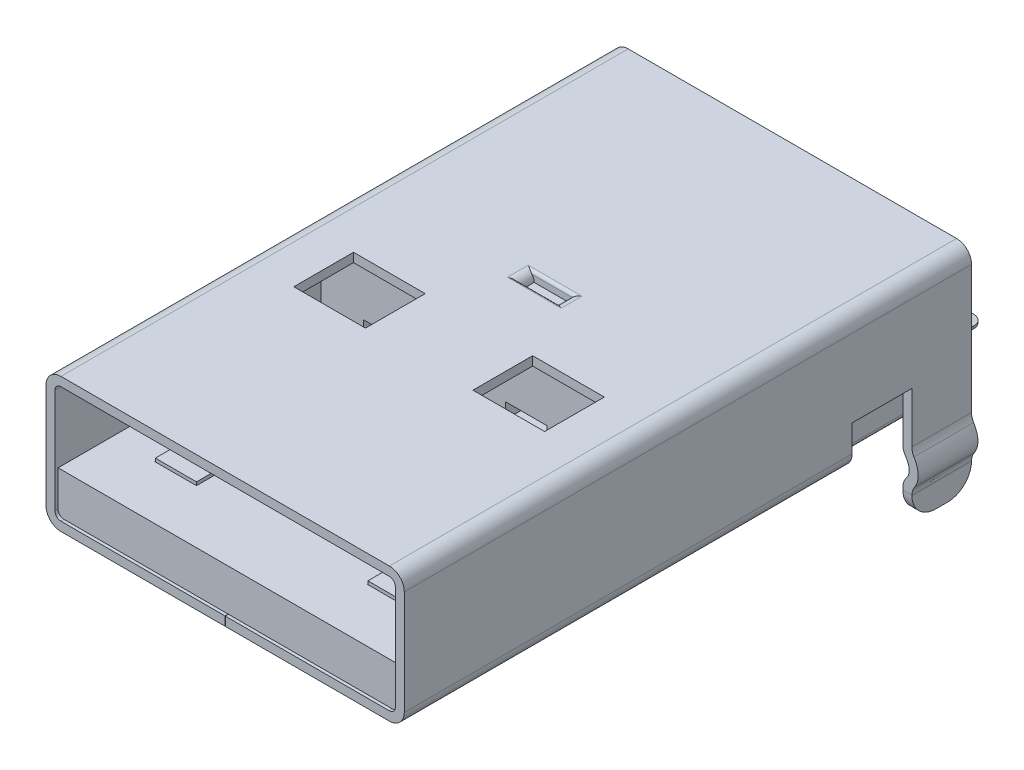
SolidWorks part; units mm, degrees
ref_plane "Front Plane" through (0, 0, 0) normal (0, 0, 1) x (1, 0, 0)
ref_plane "Top Plane" through (0, 0, 0) normal (0, 1, 0) x (1, 0, 0)
ref_plane "Right Plane" through (0, 0, 0) normal (1, 0, 0) x (0, 0, -1)
sketch "Sketch1" plane through (0, 0, 0) normal (0, 0, 1) x (1, 0, 0)
  line L4 (6, -1.75) -> (6, 1.75)
  line L5 (5.5, 2.25) -> (-5.5, 2.25)
  line L6 (-6, 1.75) -> (-6, -1.75)
  line L15 (-5.5, -2.25) -> (5.5, -2.25)
  line L16 (-5.5, -1.95) -> (5.5, -1.95)
  line L17 (5.7, -1.75) -> (5.7, 1.75)
  line L18 (5.5, 1.95) -> (-5.5, 1.95)
  line L19 (-5.7, 1.75) -> (-5.7, -1.75)
  arc A0 (5.5, -2.25) -> (6, -1.75) centre (5.5, -1.75) ccw
  arc A1 (6, 1.75) -> (5.5, 2.25) centre (5.5, 1.75) ccw
  arc A2 (-5.5, 2.25) -> (-6, 1.75) centre (-5.5, 1.75) ccw
  arc A3 (-6, -1.75) -> (-5.5, -2.25) centre (-5.5, -1.75) ccw
  arc A7 (5.5, -1.95) -> (5.7, -1.75) centre (5.5, -1.75) ccw
  arc A8 (5.7, 1.75) -> (5.5, 1.95) centre (5.5, 1.75) ccw
  arc A9 (-5.5, 1.95) -> (-5.7, 1.75) centre (-5.5, 1.75) ccw
  arc A10 (-5.7, -1.75) -> (-5.5, -1.95) centre (-5.5, -1.75) ccw
extrude "Boss-Extrude1" add sketch "Sketch1" against normal blind 19
sketch "Sketch2" plane through (6, 0, 0) normal (1, 0, 0) x (0, 0, -1)
  line L0 (17, -1.25) -> (17, -0.85)
  line L1 (17, -0.85) -> (15, -0.85)
  line L2 (15, -2.25) -> (15, -1.75)
  line L3 (15, -0.85) -> (15, -1.75)
  line L4 (17, -1.25) -> (17, -1.75)
  line L5 (19, -2.25) -> (0, -2.25) construction
  line L6 (17, -2.25) -> (15, -2.25)
  line L7 (17, -1.75) -> (19, -1.75)
  line L8 (19, -1.75) -> (19, -2.25)
  line L9 (19, -2.25) -> (17, -2.25)
extrude "Cut-Extrude1" cut sketch "Sketch2" against normal through all
sketch "Sketch3" plane through (0, 0, -17) normal (0, 0, 1) x (1, 0, 0)
  line L0 (5.7, -3.9471) -> (5.7, -4.7471)
  line L1 (5.7, -4.7471) -> (6, -4.7471)
  line L2 (6, -4.7471) -> (6, -3.9598)
  line L3 (-6, -3.9598) -> (-6, -4.7471)
  line L4 (-6, -4.7471) -> (-5.7, -4.7471)
  line L5 (-5.7, -4.7471) -> (-5.7, -3.9471)
  line L6 (6, -2.5479) -> (6, -1.75)
  line L7 (5.7, -1.75) -> (5.7, -2.6346)
  line L8 (5.7, -3.8595) -> (5.7, -3.9471)
  line L9 (-6, -1.75) -> (-6, -2.5479)
  line L10 (-5.7, -3.9471) -> (-5.7, -3.8595)
  line L11 (-5.7, -2.6346) -> (-5.7, -1.75)
  line L12 (6, -1.75) -> (5.7, -1.75)
  line L13 (-6, -1.75) -> (-5.7, -1.75)
  spline S0 degree 3 poles (6, -3.9598) (6, -3.9556) (6.0001, -3.9513) (6.0002, -3.9471) knots 0 0 0 0 0.000013 0.000013 0.000013 0.000013 weights 1 1 1 1
  spline S1 degree 3 poles (-6.0002, -3.9471) (-6.0001, -3.9513) (-6, -3.9556) (-6, -3.9598) knots 0 0 0 0 0.000013 0.000013 0.000013 0.000013 weights 1 1 1 1
  spline S2 degree 3 poles (6.0707, -2.8043) (6.0247, -2.7272) (6, -2.6376) (6, -2.5479) knots 0 0 0 0 0.000269 0.000269 0.000269 0.000269 weights 1 1 1 1
  spline S3 degree 3 poles (5.7, -2.6346) (5.7, -2.7328) (5.7297, -2.8307) (5.7842, -2.9124) knots 0 0 0 0 0.000295 0.000295 0.000295 0.000295 weights 1 1 1 1
  spline S4 degree 3 poles (5.7842, -2.9124) (5.8959, -3.0796) (5.9405, -3.3024) (5.8728, -3.4711) (5.8159, -3.5394) knots 0 0 0 0 0.000386 0.000676 0.000676 0.000676 0.000676 weights 1 1 1 1 1
  spline S5 degree 3 poles (5.8159, -3.5394) (5.7418, -3.6283) (5.7, -3.7437) (5.7, -3.8595) knots 0 0 0 0 0.000348 0.000348 0.000348 0.000348 weights 1 1 1 1
  spline S6 degree 3 poles (6.0002, -3.9471) (6.0027, -3.851) (6.0335, -3.7558) (6.0879, -3.6766) knots 0 0 0 0 0.000288 0.000288 0.000288 0.000288 weights 1 1 1 1
  spline S7 degree 3 poles (6.0879, -3.6766) (6.255, -3.4335) (6.2625, -3.1253) (6.0707, -2.8043) knots 0 0 0 0 0.000918 0.000918 0.000918 0.000918 weights 1 1 1 1
  spline S8 degree 3 poles (-6, -2.5479) (-6, -2.6376) (-6.0247, -2.7272) (-6.0707, -2.8043) knots 0 0 0 0 0.000269 0.000269 0.000269 0.000269 weights 1 1 1 1
  spline S9 degree 3 poles (-6.0707, -2.8043) (-6.2625, -3.1253) (-6.255, -3.4335) (-6.0879, -3.6766) knots 0 0 0 0 0.00092 0.00092 0.00092 0.00092 weights 1 1 1 1
  spline S10 degree 3 poles (-6.0879, -3.6766) (-6.0335, -3.7558) (-6.0027, -3.851) (-6.0002, -3.9471) knots 0 0 0 0 0.000289 0.000289 0.000289 0.000289 weights 1 1 1 1
  spline S11 degree 3 poles (-5.7, -3.8595) (-5.7, -3.7437) (-5.7418, -3.6283) (-5.8159, -3.5394) knots 0 0 0 0 0.000348 0.000348 0.000348 0.000348 weights 1 1 1 1
  spline S12 degree 3 poles (-5.8159, -3.5394) (-5.8538, -3.4938) (-5.904, -3.3995) (-5.9248, -3.2089) (-5.868, -3.0378) (-5.7842, -2.9124) knots 0 0 0 0 0.000194 0.000388 0.000679 0.000679 0.000679 0.000679 weights 1 1 1 1 1 1
  spline S13 degree 3 poles (-5.7842, -2.9124) (-5.7297, -2.8307) (-5.7, -2.7328) (-5.7, -2.6346) knots 0 0 0 0 0.000295 0.000295 0.000295 0.000295 weights 1 1 1 1
  point P28 (6, -1.75)
extrude "Boss-Extrude2" add sketch "Sketch3" against normal up to surface (2 mm away) up to face at (0, 0.7242, -19)
fillet "Fillet1" radius 0.8 4 edges at (-5.85, -4.7471, -17) (-5.85, -4.7471, -19) (5.85, -4.7471, -17) (5.85, -4.7471, -19)
sketch "Sketch4" plane through (0, 2.25, 0) normal (0, 1, 0) x (1, 0, 0)
  line L0 (-1.8, 6.5) -> (-4.2, 6.5)
  line L1 (-4.2, 6.5) -> (-4.2, 8.5)
  line L2 (-4.2, 8.5) -> (-1.8, 8.5)
  line L3 (1.8, 6.5) -> (1.8, 8.5)
  line L4 (4.2, 6.5) -> (1.8, 6.5)
  line L5 (4.2, 8.5) -> (4.2, 6.5)
  line L6 (1.8, 8.5) -> (4.2, 8.5)
  line L7 (-1.8, 8.5) -> (-1.8, 6.5)
extrude "Cut-Extrude2" cut sketch "Sketch4" against normal through all
sketch "Sketch5" plane through (0, -2.25, 0) normal (0, -1, 0) x (1, 0, 0)
  line L1 (0.1311, -3.1511) -> (0.6409, -2.9635)
  line L2 (0.91, -3.1511) -> (0.91, -4.3489)
  line L3 (0.6409, -4.5365) -> (0.1311, -4.3489)
  line L5 (0.1311, -10.6511) -> (0.6409, -10.4635)
  line L6 (0.91, -10.6511) -> (0.91, -11.8489)
  line L7 (0.6409, -12.0365) -> (0.1311, -11.8489)
  line L10 (0.1345, -3.1605) -> (0.6444, -2.9728)
  line L11 (0.9, -3.1511) -> (0.9, -4.3489)
  line L12 (0.6444, -4.5272) -> (0.1345, -4.3395)
  line L14 (0.1345, -10.6605) -> (0.6444, -10.4728)
  line L15 (0.9, -10.6511) -> (0.9, -11.8489)
  line L16 (0.6444, -12.0272) -> (0.1345, -11.8395)
  line L19 (0.005, 0) -> (-0.005, 0)
  line L20 (0, -3.0666) -> (-0.005, 0)
  line L21 (0.01, -11.9334) -> (0.01, -15)
  line L22 (-5.5, -15) -> (5.5, -15) construction
  line L23 (0, -11.9334) -> (0, -15)
  line L24 (0.01, -3.0666) -> (0.005, 0)
  line L25 (0.01, -4.4334) -> (0.01, -10.5666)
  line L26 (0, -15) -> (0.01, -15)
  line L27 (0, -10.5666) -> (0, -4.4334)
  arc A0 (0.01, -3.0666) -> (0.1311, -3.1511) centre (0.1, -3.0666) ccw
  arc A1 (0.91, -3.1511) -> (0.6409, -2.9635) centre (0.71, -3.1511) ccw
  arc A2 (0.6409, -4.5365) -> (0.91, -4.3489) centre (0.71, -4.3489) ccw
  arc A3 (0.1311, -4.3489) -> (0.01, -4.4334) centre (0.1, -4.4334) ccw
  arc A4 (0.01, -10.5666) -> (0.1311, -10.6511) centre (0.1, -10.5666) ccw
  arc A5 (0.91, -10.6511) -> (0.6409, -10.4635) centre (0.71, -10.6511) ccw
  arc A6 (0.6409, -12.0365) -> (0.91, -11.8489) centre (0.71, -11.8489) ccw
  arc A7 (0.1311, -11.8489) -> (0.01, -11.9334) centre (0.1, -11.9334) ccw
  arc A8 (0, -3.0666) -> (0.1345, -3.1605) centre (0.1, -3.0666) ccw
  arc A9 (0.9, -3.1511) -> (0.6444, -2.9728) centre (0.71, -3.1511) ccw
  arc A10 (0.6444, -4.5272) -> (0.9, -4.3489) centre (0.71, -4.3489) ccw
  arc A11 (0.1345, -4.3395) -> (0, -4.4334) centre (0.1, -4.4334) ccw
  arc A12 (0, -10.5666) -> (0.1345, -10.6605) centre (0.1, -10.5666) ccw
  arc A13 (0.9, -10.6511) -> (0.6444, -10.4728) centre (0.71, -10.6511) ccw
  arc A14 (0.6444, -12.0272) -> (0.9, -11.8489) centre (0.71, -11.8489) ccw
  arc A15 (0.1345, -11.8395) -> (0, -11.9334) centre (0.1, -11.9334) ccw
  point P54 (0, 0)
extrude "Cut-Extrude3" cut sketch "Sketch5" against normal blind 0.3
sketch "Sketch6" plane through (0, 0, 0) normal (0, 0, 1) x (1, 0, 0)
  line L1 (-5.5, -1.945) -> (5.5, -1.945)
  line L4 (5.695, -0.55) -> (-5.695, -0.55)
  line L6 (5.695, -1.75) -> (5.695, -0.55)
  line L8 (-5.695, -0.55) -> (-5.695, -1.75)
  line L9 (5.695, -0.555) -> (-5.695, -0.555) construction
  line L10 (-5.7, -0.55) -> (-5.7, -1.75) construction
  line L11 (-5.5, -1.95) -> (5.5, -1.95) construction
  line L12 (5.7, -1.75) -> (5.7, -0.55) construction
  line L13 (5.695, -1.75) -> (5.695, -0.555) construction
  line L14 (5.7, -0.55) -> (-5.7, -0.55) construction
  line L15 (-5.695, -0.555) -> (-5.695, -1.75) construction
  arc A4 (5.5, -1.945) -> (5.695, -1.75) centre (5.5, -1.75) ccw
  arc A5 (-5.695, -1.75) -> (-5.5, -1.945) centre (-5.5, -1.75) ccw
  arc A6 (-5.7, -1.75) -> (-5.5, -1.95) centre (-5.5, -1.75) ccw construction
  arc A7 (5.5, -1.95) -> (5.7, -1.75) centre (5.5, -1.75) ccw construction
extrude "Boss-Extrude3" add sketch "Sketch6" against normal blind 18.8 separate body
sketch "Sketch7" plane through (0, -0.55, 0) normal (0, 1, 0) x (1, 0, 0)
  line L0 (-2.8595, 1.9) -> (-2.8595, 14.314)
  line L1 (-2.8595, 14.314) -> (-4.2595, 14.314)
  line L2 (-4.2595, 14.314) -> (-4.2595, 1.9)
  line L3 (-4.2595, 1.9) -> (-2.8595, 1.9)
  line L4 (-0.4865, 3.814) -> (-0.4865, 14.314)
  line L5 (-0.4865, 14.314) -> (-1.8865, 14.314)
  line L6 (-1.8865, 14.314) -> (-1.8865, 3.814)
  line L8 (1.8865, 3.814) -> (1.8865, 14.314)
  line L9 (1.8865, 14.314) -> (0.4865, 14.314)
  line L10 (0.4865, 14.314) -> (0.4865, 3.814)
  line L12 (4.2595, 1.9) -> (4.2595, 14.314)
  line L13 (4.2595, 14.314) -> (2.8595, 14.314)
  line L14 (2.8595, 14.314) -> (2.8595, 1.9)
  line L15 (2.8595, 1.9) -> (4.2595, 1.9)
  line L17 (-1.8865, 3.814) -> (-0.4865, 3.814)
  line L18 (0.4865, 3.814) -> (1.8865, 3.814)
extrude "Cut-Extrude4" cut sketch "Sketch7" against normal blind 0.11
sketch "Sketch8" plane through (2.8595, 0, 0) normal (1, 0, 0) x (0, 0, -1)
  line L2 (14.314, -0.66) -> (14.314, -0.55)
  line L4 (18.8, -1.4856) -> (18.9137, -1.4856)
  line L5 (18.9137, -1.4856) -> (18.9137, -1.5935)
  line L6 (18.9137, -1.5935) -> (18.8, -1.5935)
  line L7 (14.314, -0.55) -> (15.314, -0.55)
  line L8 (18.8, -0.55) -> (0, -0.55) construction
  line L9 (15.314, -0.55) -> (15.314, -0.7935)
  spline S0 degree 3 poles (14.314, -0.66) (15.3904, -0.9279) (17.2747, -1.3557) (18.3201, -1.5258) (18.8, -1.5935) knots 0 0 0 0 0.001964 0.004583 0.004583 0.004583 0.004583 weights 1 1 1 1 1
  spline S1 degree 3 poles (18.8, -1.4856) (18.3206, -1.4177) (17.427, -1.2717) (15.9172, -0.9366) (15.314, -0.7935) knots 0 0 0 0 0.00262 0.003924 0.003924 0.003924 0.003924 weights 1 1 1 1 1
  point P4 (14.314, -0.66)
extrude "Cut-Extrude5" cut sketch "Sketch8" along normal blind 1.4
sketch "Sketch9" plane through (0.4865, 0, 0) normal (1, 0, 0) x (0, 0, -1)
  line L4 (14.314, -0.66) -> (14.314, -0.55)
  line L5 (18.8, -1.4856) -> (18.9137, -1.4856)
  line L6 (18.9137, -1.4856) -> (18.9137, -1.5935)
  line L7 (18.9137, -1.5935) -> (18.8, -1.5935)
  line L8 (14.314, -0.55) -> (15.314, -0.55)
  line L9 (15.314, -0.55) -> (15.314, -0.7935)
  spline S0 degree 3 poles (14.314, -0.66) (15.3904, -0.9279) (17.2747, -1.3557) (18.3201, -1.5258) (18.8, -1.5935) knots 0 0 0 0 0.001964 0.004583 0.004583 0.004583 0.004583 weights 1 1 1 1 1
  spline S1 degree 3 poles (18.8, -1.4856) (18.3206, -1.4177) (17.427, -1.2717) (15.9172, -0.9366) (15.314, -0.7935) knots 0 0 0 0 0.00262 0.003924 0.003924 0.003924 0.003924 weights 1 1 1 1 1
  point P4 (14.314, -0.66)
  point P10 (14.314, -0.55)
extrude "Cut-Extrude6" cut sketch "Sketch9" along normal blind 1.4
sketch "Sketch10" plane through (-1.8865, 0, 0) normal (1, 0, 0) x (0, 0, -1)
  line L4 (14.314, -0.66) -> (14.314, -0.55)
  line L5 (18.8, -1.4856) -> (18.9137, -1.4856)
  line L6 (18.9137, -1.4856) -> (18.9137, -1.5935)
  line L7 (18.9137, -1.5935) -> (18.8, -1.5935)
  line L8 (14.314, -0.55) -> (15.314, -0.55)
  line L9 (15.314, -0.55) -> (15.314, -0.7935)
  spline S0 degree 3 poles (14.314, -0.66) (15.3904, -0.9279) (17.2747, -1.3557) (18.3201, -1.5258) (18.8, -1.5935) knots 0 0 0 0 0.001964 0.004583 0.004583 0.004583 0.004583 weights 1 1 1 1 1
  spline S1 degree 3 poles (18.8, -1.4856) (18.3206, -1.4177) (17.427, -1.2717) (15.9172, -0.9366) (15.314, -0.7935) knots 0 0 0 0 0.00262 0.003924 0.003924 0.003924 0.003924 weights 1 1 1 1 1
  point P4 (14.314, -0.66)
  point P9 (14.314, -0.55)
extrude "Cut-Extrude7" cut sketch "Sketch10" along normal blind 1.4
sketch "Sketch11" plane through (-4.2595, 0, 0) normal (1, 0, 0) x (0, 0, -1)
  line L4 (14.314, -0.66) -> (14.314, -0.55)
  line L5 (18.8, -1.4856) -> (18.9137, -1.4856)
  line L6 (18.9137, -1.4856) -> (18.9137, -1.5935)
  line L7 (18.9137, -1.5935) -> (18.8, -1.5935)
  line L8 (14.314, -0.55) -> (15.314, -0.55)
  line L9 (15.314, -0.55) -> (15.314, -0.7935)
  spline S0 degree 3 poles (14.314, -0.66) (15.3904, -0.9279) (17.2747, -1.3557) (18.3201, -1.5258) (18.8, -1.5935) knots 0 0 0 0 0.001964 0.004583 0.004583 0.004583 0.004583 weights 1 1 1 1 1
  spline S1 degree 3 poles (18.8, -1.4856) (18.3206, -1.4177) (17.427, -1.2717) (15.9172, -0.9366) (15.314, -0.7935) knots 0 0 0 0 0.00262 0.003924 0.003924 0.003924 0.003924 weights 1 1 1 1 1
  point P4 (14.314, -0.66)
  point P10 (14.314, -0.55)
extrude "Cut-Extrude8" cut sketch "Sketch11" along normal blind 1.4
sketch "Sketch13" plane through (0, 0, -18.8) normal (0, 0, -1) x (-1, 0, 0)
  line L0 (5.69, -0.55) -> (-5.69, -0.55)
  line L6 (-5.5, 1.94) -> (5.5, 1.94)
  line L10 (-5.69, -0.55) -> (-5.69, 1.75)
  line L11 (5.69, 1.75) -> (5.69, -0.55)
  arc A4 (-5.5, 1.94) -> (-5.69, 1.75) centre (-5.5, 1.75) ccw
  arc A5 (5.69, 1.75) -> (5.5, 1.94) centre (5.5, 1.75) ccw
  point P4 (-5.695, -0.55)
  point P9 (0.005, 1.99)
extrude "Boss-Extrude4" add sketch "Sketch13" against normal blind 9.9
sketch "Sketch14" plane through (0, 0, -8.9) normal (0, 0, 1) x (1, 0, 0)
  line L0 (-4.2595, -0.55) -> (-2.8595, -0.55) construction
  line L4 (-1.8865, -0.55) -> (-0.4865, -0.55) construction
  line L8 (0.4865, -0.55) -> (1.8865, -0.55) construction
  line L12 (2.8595, -0.55) -> (4.2595, -0.55) construction
  line L16 (-4.2595, -0.55) -> (-2.8595, -0.55)
  line L20 (-1.8865, -0.55) -> (-0.4865, -0.55)
  line L24 (0.4865, -0.55) -> (1.8865, -0.55)
  line L28 (2.8595, -0.55) -> (4.2595, -0.55)
  line L32 (-4.2595, -0.55) -> (-4.2595, -0.44)
  line L33 (-4.2595, -0.44) -> (-2.8595, -0.44)
  line L34 (-2.8595, -0.44) -> (-2.8595, -0.55)
  line L35 (-1.8865, -0.55) -> (-1.8865, -0.44)
  line L36 (-1.8865, -0.44) -> (-0.4865, -0.44)
  line L37 (-0.4865, -0.44) -> (-0.4865, -0.55)
  line L38 (0.4865, -0.55) -> (0.4865, -0.44)
  line L39 (0.4865, -0.44) -> (1.8865, -0.44)
  line L40 (1.8865, -0.44) -> (1.8865, -0.55)
  line L41 (2.8595, -0.55) -> (2.8595, -0.44)
  line L42 (2.8595, -0.44) -> (4.2595, -0.44)
  line L43 (4.2595, -0.44) -> (4.2595, -0.55)
extrude "Cut-Extrude10" cut sketch "Sketch14" against normal blind 6.41
sketch "Sketch15" plane through (0, 0, -8.9) normal (0, 0, 1) x (1, 0, 0)
  line L0 (-4.2595, -0.44) -> (-4.2595, 0.06)
  line L1 (-4.2595, 0.06) -> (-2.8595, 0.06)
  line L2 (-2.8595, 0.06) -> (-2.8595, -0.44)
  line L3 (-2.8595, -0.44) -> (-4.2595, -0.44)
  line L4 (-1.8865, -0.44) -> (-1.8865, 0.06)
  line L5 (-0.4865, -0.44) -> (-0.4865, 0.06)
  line L6 (0.4865, -0.44) -> (0.4865, 0.06)
  line L7 (1.8865, -0.44) -> (1.8865, 0.06)
  line L8 (2.8595, -0.44) -> (2.8595, 0.06)
  line L9 (4.2595, -0.44) -> (4.2595, 0.06)
  line L10 (4.2595, 0.06) -> (2.8595, 0.06)
  line L11 (2.8595, -0.44) -> (4.2595, -0.44)
  line L12 (1.8865, 0.06) -> (0.4865, 0.06)
  line L13 (0.4865, -0.44) -> (1.8865, -0.44)
  line L14 (-0.4865, 0.06) -> (-1.8865, 0.06)
  line L15 (-1.8865, -0.44) -> (-0.4865, -0.44)
extrude "Cut-Extrude11" cut sketch "Sketch15" against normal blind 2.5
sketch "Sketch16" plane through (0, 0, -8.9) normal (0, 0, 1) x (1, 0, 0)
  line L1 (-5.5, 1.94) -> (5.5, 1.94) construction
  line L2 (-1, 1.59) -> (1, 1.59)
  line L3 (-1, 1.59) -> (-1, 1.94)
  line L4 (-1, 1.94) -> (1, 1.94)
  line L5 (1, 1.94) -> (1, 1.59)
  point P8 (0, 1.59)
extrude "Cut-Extrude12" cut sketch "Sketch16" against normal blind 2.5
sketch "Sketch17" plane through (0, 1.95, 0) normal (0, -1, 0) x (1, 0, 0)
  line L1 (-0.6, -10.3013) -> (0.6, -10.3013)
  line L10 (-0.6, -11.1013) -> (0.6, -11.1013)
  line L12 (-0.6, -11.1013) -> (-0.6, -10.3013)
  line L13 (0.6, -11.1013) -> (0.6, -10.3013)
extrude "Boss-Extrude5" add sketch "Sketch17" along normal blind 0.3
fillet "Fillet2" radius 0.3 2 edges at (-0.6, 1.95, -10.7013) (0.6, 1.95, -10.7013)
fillet "Fillet5" radius 0.1 4 edges at (0.6, 1.65, -10.7013) (0, 1.65, -11.1013) (-0.6, 1.65, -10.7013) (0, 1.65, -10.3013)
sketch "Sketch19" plane through (0, 2.25, 0) normal (0, 1, 0) x (1, 0, 0)
  line L2 (-0.6, 10.9513) -> (0.6, 10.9513)
  line L3 (-0.6, 10.4513) -> (0.6, 10.4513)
  line L4 (-0.6, 10.3013) -> (0.6, 10.3013)
  line L5 (0.6, 10.3013) -> (0.6, 11.1013)
  line L6 (0.6, 11.1013) -> (-0.6, 11.1013)
  line L7 (-0.6, 11.1013) -> (-0.6, 10.3013)
  line L9 (0.6, 10.4513) -> (0.6, 10.9513)
  line L11 (-0.6, 10.9513) -> (-0.6, 10.4513)
  dimension "D1" = 0
extrude "Cut-Extrude14" cut sketch "Sketch19" against normal blind 0.3
fillet "Fillet6" radius 0.3 2 edges at (0.6, 2.25, -10.7013) (-0.6, 2.25, -10.7013)
fillet "Fillet7" radius 0.1 2 edges at (0, 2.25, -10.4513) (0, 2.25, -10.9513)
ref_plane "Plane1" through (0, -0.65, 0) normal (0, 1, 0) x (1, 0, 0)
sketch "Sketch21" plane through (0, -0.65, 0) normal (0, 1, 0) x (1, 0, 0)
  line L32 (2.8695, 1.91) -> (4.2495, 1.91)
  line L33 (4.2495, 1.91) -> (4.2495, 14.304)
  line L34 (4.2495, 14.304) -> (2.8695, 14.304)
  line L35 (2.8695, 14.304) -> (2.8695, 1.91)
  line L36 (1.8765, 14.304) -> (0.4965, 14.304)
  line L37 (0.4965, 14.304) -> (0.4965, 3.824)
  line L38 (0.4965, 3.824) -> (1.8765, 3.824)
  line L39 (1.8765, 3.824) -> (1.8765, 14.304)
  line L40 (-0.4965, 14.304) -> (-1.8765, 14.304)
  line L41 (-1.8765, 14.304) -> (-1.8765, 3.824)
  line L42 (-1.8765, 3.824) -> (-0.4965, 3.824)
  line L43 (-0.4965, 3.824) -> (-0.4965, 14.304)
  line L44 (-4.2495, 1.91) -> (-2.8695, 1.91)
  line L45 (-2.8695, 1.91) -> (-2.8695, 14.304)
  line L46 (-2.8695, 14.304) -> (-4.2495, 14.304)
  line L47 (-4.2495, 14.304) -> (-4.2495, 1.91)
extrude "Boss-Extrude6" add sketch "Sketch21" along normal blind 0.2 separate body
sketch "Sketch22" plane through (4.2495, 0, 0) normal (1, 0, 0) x (0, 0, -1)
  line L5 (14.324, -0.6519) -> (14.304, -0.65)
  line L8 (15.304, -0.8009) -> (14.304, -0.5637)
  line L9 (14.304, -0.45) -> (14.304, -0.65) construction
  line L10 (14.304, -0.5637) -> (14.304, -0.65)
  line L12 (18.79, -1.5812) -> (18.8, -1.5826)
  line L13 (18.8, -1.75) -> (18.8, -0.55) construction
  line L16 (18.79, -1.4938) -> (18.8, -1.4952)
  line L17 (18.8, -1.4952) -> (18.8, -1.5826)
  spline S6 degree 3 poles (14.324, -0.6519) (14.4743, -0.6892) (14.7829, -0.7653) (15.3376, -0.899) (15.9637, -1.0446) (16.6098, -1.1869) (17.3599, -1.342) (17.9635, -1.453) (18.4673, -1.5343) (18.679, -1.5655) (18.79, -1.5812) knots 0.000005 0.000005 0.000005 0.000005 0.00029 0.000574 0.001144 0.001714 0.002284 0.003423 0.003993 0.004563 0.004563 0.004563 0.004563
  spline S7 degree 3 poles (18.79, -1.4938) (18.5908, -1.4655) (18.227, -1.4102) (17.4801, -1.2776) (16.701, -1.1186) (15.9616, -0.9549) (15.5167, -0.8514) (15.304, -0.8009) knots 0.000016 0.000016 0.000016 0.000016 0.000994 0.001972 0.002951 0.00344 0.003929 0.003929 0.003929 0.003929
extrude "Boss-Extrude7" add sketch "Sketch22" against normal blind 1.38
sketch "Sketch23" plane through (1.8765, 0, 0) normal (1, 0, 0) x (0, 0, -1)
  line L0 (14.324, -0.6519) -> (14.304, -0.65)
  line L1 (15.304, -0.8009) -> (14.304, -0.5637)
  line L2 (14.304, -0.5637) -> (14.304, -0.65)
  line L3 (18.79, -1.5812) -> (18.8, -1.5826)
  line L4 (18.79, -1.4938) -> (18.8, -1.4952)
  line L5 (18.8, -1.4952) -> (18.8, -1.5826)
  spline S0 degree 3 poles (14.324, -0.6519) (14.4743, -0.6892) (14.7829, -0.7653) (15.3376, -0.899) (15.9637, -1.0446) (16.6098, -1.1869) (17.3599, -1.342) (17.9635, -1.453) (18.4673, -1.5343) (18.679, -1.5655) (18.79, -1.5812) knots 0.000005 0.000005 0.000005 0.000005 0.00029 0.000574 0.001144 0.001714 0.002284 0.003423 0.003993 0.004563 0.004563 0.004563 0.004563
  spline S1 degree 3 poles (18.79, -1.4938) (18.5908, -1.4655) (18.227, -1.4102) (17.4801, -1.2776) (16.701, -1.1186) (15.9616, -0.9549) (15.5167, -0.8514) (15.304, -0.8009) knots 0.000016 0.000016 0.000016 0.000016 0.000994 0.001972 0.002951 0.00344 0.003929 0.003929 0.003929 0.003929
  point P8 (14.304, -0.65)
extrude "Boss-Extrude8" add sketch "Sketch23" against normal blind 1.38
sketch "Sketch24" plane through (-0.4965, 0, 0) normal (1, 0, 0) x (0, 0, -1)
  line L0 (14.324, -0.6519) -> (14.304, -0.65)
  line L1 (15.304, -0.8009) -> (14.304, -0.5637)
  line L2 (14.304, -0.5637) -> (14.304, -0.65)
  line L3 (18.79, -1.5812) -> (18.8, -1.5826)
  line L4 (18.79, -1.4938) -> (18.8, -1.4952)
  line L5 (18.8, -1.4952) -> (18.8, -1.5826)
  spline S0 degree 3 poles (14.324, -0.6519) (14.4743, -0.6892) (14.7829, -0.7653) (15.3376, -0.899) (15.9637, -1.0446) (16.6098, -1.1869) (17.3599, -1.342) (17.9635, -1.453) (18.4673, -1.5343) (18.679, -1.5655) (18.79, -1.5812) knots 0.000005 0.000005 0.000005 0.000005 0.00029 0.000574 0.001144 0.001714 0.002284 0.003423 0.003993 0.004563 0.004563 0.004563 0.004563
  spline S1 degree 3 poles (18.79, -1.4938) (18.5908, -1.4655) (18.227, -1.4102) (17.4801, -1.2776) (16.701, -1.1186) (15.9616, -0.9549) (15.5167, -0.8514) (15.304, -0.8009) knots 0.000016 0.000016 0.000016 0.000016 0.000994 0.001972 0.002951 0.00344 0.003929 0.003929 0.003929 0.003929
  point P8 (14.304, -0.65)
extrude "Boss-Extrude9" add sketch "Sketch24" against normal blind 1.38
sketch "Sketch25" plane through (-2.8695, 0, 0) normal (1, 0, 0) x (0, 0, -1)
  line L0 (14.324, -0.6519) -> (14.304, -0.65)
  line L1 (15.304, -0.8009) -> (14.304, -0.5637)
  line L2 (14.304, -0.5637) -> (14.304, -0.65)
  line L3 (18.79, -1.5812) -> (18.8, -1.5826)
  line L4 (18.79, -1.4938) -> (18.8, -1.4952)
  line L5 (18.8, -1.4952) -> (18.8, -1.5826)
  spline S0 degree 3 poles (14.324, -0.6519) (14.4743, -0.6892) (14.7829, -0.7653) (15.3376, -0.899) (15.9637, -1.0446) (16.6098, -1.1869) (17.3599, -1.342) (17.9635, -1.453) (18.4673, -1.5343) (18.679, -1.5655) (18.79, -1.5812) knots 0.000005 0.000005 0.000005 0.000005 0.00029 0.000574 0.001144 0.001714 0.002284 0.003423 0.003993 0.004563 0.004563 0.004563 0.004563
  spline S1 degree 3 poles (18.79, -1.4938) (18.5908, -1.4655) (18.227, -1.4102) (17.4801, -1.2776) (16.701, -1.1186) (15.9616, -0.9549) (15.5167, -0.8514) (15.304, -0.8009) knots 0.000016 0.000016 0.000016 0.000016 0.000994 0.001972 0.002951 0.00344 0.003929 0.003929 0.003929 0.003929
  point P8 (14.304, -0.65)
extrude "Boss-Extrude10" add sketch "Sketch25" against normal blind 1.38
chamfer "Chamfer1" distance 0.1 angle 45 1 edges at (3.5595, -0.45, -14.304)
chamfer "Chamfer2" distance 0.1 angle 45 1 edges at (1.1865, -0.45, -14.304)
chamfer "Chamfer3" distance 0.1 angle 45 1 edges at (-1.1865, -0.45, -14.304)
chamfer "Chamfer4" distance 0.1 angle 45 1 edges at (-3.5595, -0.45, -14.304)
ref_plane "Plane3" through (3.5595, 0, 0) normal (1, 0, 0) x (0, 0, -1)
sketch "Sketch27" plane through (3.5595, 0, 0) normal (1, 0, 0) x (0, 0, -1)
  line L0 (21.1217, -2.2241) -> (21.4959, -2.2475)
  line L2 (21.5022, -2.1603) -> (21.1279, -2.1369)
  line L3 (20.773, -2.2023) -> (21.1217, -2.2241)
  line L4 (21.1279, -2.1369) -> (20.797, -2.1162)
  line L5 (20.6271, -2.0749) -> (19.4035, -1.5374)
  line L6 (19.2024, -1.4952) -> (18.8, -1.4952)
  line L7 (18.8, -1.4952) -> (18.8, -1.5826)
  line L8 (18.8, -1.5826) -> (19.1814, -1.5826)
  line L9 (19.3825, -1.6248) -> (20.6031, -2.1611)
  line L11 (21.5022, -2.1603) -> (21.4959, -2.2475)
  arc A0 (20.6031, -2.1611) -> (20.773, -2.2023) centre (20.8042, -1.7033) ccw
  arc A1 (20.6271, -2.0749) -> (20.797, -2.1162) centre (20.8282, -1.6172) ccw
  arc A2 (19.4035, -1.5374) -> (19.2024, -1.4952) centre (19.2024, -1.9952) ccw
  arc A3 (19.3825, -1.6248) -> (19.1814, -1.5826) centre (19.1814, -2.0826) ccw
  point P7 (18.8, -1.4952)
  point P20 (18.8, -1.5826)
extrude "Boss-Extrude11" add sketch "Sketch27" along normal mid plane 0.75
ref_plane "Plane4" through (1.1865, 0, 0) normal (1, 0, 0) x (0, 0, -1)
sketch "Sketch28" plane through (1.1865, 0, 0) normal (1, 0, 0) x (0, 0, -1)
  line L0 (21.1216, -2.2243) -> (21.4959, -2.2477)
  line L1 (21.5021, -2.1605) -> (21.1278, -2.1371)
  line L2 (20.773, -2.2025) -> (21.1216, -2.2243)
  line L3 (21.1278, -2.1371) -> (20.7969, -2.1164)
  line L4 (20.627, -2.0752) -> (19.4034, -1.5376)
  line L8 (19.3824, -1.6251) -> (20.6031, -2.1613)
  line L9 (21.5021, -2.1605) -> (21.4959, -2.2477)
  line L10 (19.1808, -1.5826) -> (18.8, -1.5826)
  line L11 (19.2023, -1.4954) -> (18.8, -1.4954)
  line L12 (18.8, -1.4954) -> (18.8, -1.5826)
  arc A0 (20.6031, -2.1613) -> (20.773, -2.2025) centre (20.8042, -1.7035) ccw
  arc A1 (20.627, -2.0752) -> (20.7969, -2.1164) centre (20.8281, -1.6174) ccw
  arc A2 (19.4034, -1.5376) -> (19.2023, -1.4954) centre (19.2023, -1.9954) ccw
  arc A3 (19.3824, -1.6251) -> (19.1808, -1.5826) centre (19.1808, -2.0826) ccw
  point P20 (18.8, -1.5826)
extrude "Boss-Extrude12" add sketch "Sketch28" along normal mid plane 0.75
ref_plane "Plane5" through (-1.1865, 0, 0) normal (1, 0, 0) x (0, 0, -1)
sketch "Sketch29" plane through (-1.1865, 0, 0) normal (1, 0, 0) x (0, 0, -1)
  line L0 (21.1216, -2.2243) -> (21.4959, -2.2477)
  line L1 (21.5021, -2.1605) -> (21.1278, -2.1371)
  line L2 (20.773, -2.2025) -> (21.1216, -2.2243)
  line L3 (21.1278, -2.1371) -> (20.7969, -2.1164)
  line L4 (20.627, -2.0752) -> (19.4034, -1.5376)
  line L5 (19.3824, -1.6251) -> (20.6031, -2.1613)
  line L6 (21.5021, -2.1605) -> (21.4959, -2.2477)
  line L7 (19.1808, -1.5826) -> (18.8, -1.5826)
  line L8 (19.2023, -1.4954) -> (18.8, -1.4954)
  line L9 (18.8, -1.4954) -> (18.8, -1.5826)
  arc A0 (20.6031, -2.1613) -> (20.773, -2.2025) centre (20.8042, -1.7035) ccw
  arc A1 (20.627, -2.0752) -> (20.7969, -2.1164) centre (20.8281, -1.6174) ccw
  arc A2 (19.4034, -1.5376) -> (19.2023, -1.4954) centre (19.2023, -1.9954) ccw
  arc A3 (19.3824, -1.6251) -> (19.1808, -1.5826) centre (19.1808, -2.0826) ccw
  point P18 (18.8, -1.5826)
extrude "Boss-Extrude13" add sketch "Sketch29" along normal mid plane 0.75
ref_plane "Plane6" through (-3.5595, 0, 0) normal (1, 0, 0) x (0, 0, -1)
sketch "Sketch30" plane through (-3.5595, 0, 0) normal (1, 0, 0) x (0, 0, -1)
  line L0 (21.1216, -2.2243) -> (21.4959, -2.2477)
  line L1 (21.5021, -2.1605) -> (21.1278, -2.1371)
  line L2 (20.773, -2.2025) -> (21.1216, -2.2243)
  line L3 (21.1278, -2.1371) -> (20.7969, -2.1164)
  line L4 (20.627, -2.0752) -> (19.4034, -1.5376)
  line L5 (19.3824, -1.6251) -> (20.6031, -2.1613)
  line L6 (21.5021, -2.1605) -> (21.4959, -2.2477)
  line L7 (19.1808, -1.5826) -> (18.8, -1.5826)
  line L8 (19.2023, -1.4954) -> (18.8, -1.4954)
  line L9 (18.8, -1.4954) -> (18.8, -1.5826)
  arc A0 (20.6031, -2.1613) -> (20.773, -2.2025) centre (20.8042, -1.7035) ccw
  arc A1 (20.627, -2.0752) -> (20.7969, -2.1164) centre (20.8281, -1.6174) ccw
  arc A2 (19.4034, -1.5376) -> (19.2023, -1.4954) centre (19.2023, -1.9954) ccw
  arc A3 (19.3824, -1.6251) -> (19.1808, -1.5826) centre (19.1808, -2.0826) ccw
  point P18 (18.8, -1.5826)
extrude "Boss-Extrude14" add sketch "Sketch30" along normal mid plane 0.75
fillet "Fillet8" radius 0.375 2 edges at (3.1845, -2.2039, -21.4991) (3.9345, -2.2039, -21.4991)
fillet "Fillet9" radius 0.375 2 edges at (0.8115, -2.2041, -21.499) (1.5615, -2.2041, -21.499)
fillet "Fillet10" radius 0.375 2 edges at (-1.5615, -2.2041, -21.499) (-0.8115, -2.2041, -21.499)
fillet "Fillet11" radius 0.375 2 edges at (-3.9345, -2.2041, -21.499) (-3.1845, -2.2041, -21.499)
sketch "Sketch31" plane through (0, 0, 0) normal (0, 0, 1) x (1, 0, 0)
  line L4 (-5.5, -1.945) -> (5.5, -1.945)
  line L5 (5.695, -1.75) -> (5.695, -0.55)
  line L6 (5.695, -0.55) -> (-5.695, -0.55)
  line L7 (-5.695, -0.55) -> (-5.695, -1.75)
  line L8 (-5.5, -1.945) -> (5.5, -1.945)
  line L9 (5.695, -1.75) -> (5.695, -0.55)
  line L10 (5.695, -0.55) -> (-5.695, -0.55)
  line L11 (-5.695, -0.55) -> (-5.695, -1.75)
  arc A2 (-5.695, -1.75) -> (-5.5, -1.945) centre (-5.5, -1.75) ccw
  arc A3 (5.5, -1.945) -> (5.695, -1.75) centre (5.5, -1.75) ccw
  arc A4 (-5.695, -1.75) -> (-5.5, -1.945) centre (-5.5, -1.75) ccw
  arc A5 (5.5, -1.945) -> (5.695, -1.75) centre (5.5, -1.75) ccw
  dimension "D1" = 0
extrude "Cut-Extrude15" cut sketch "Sketch31" against normal blind 0.1
